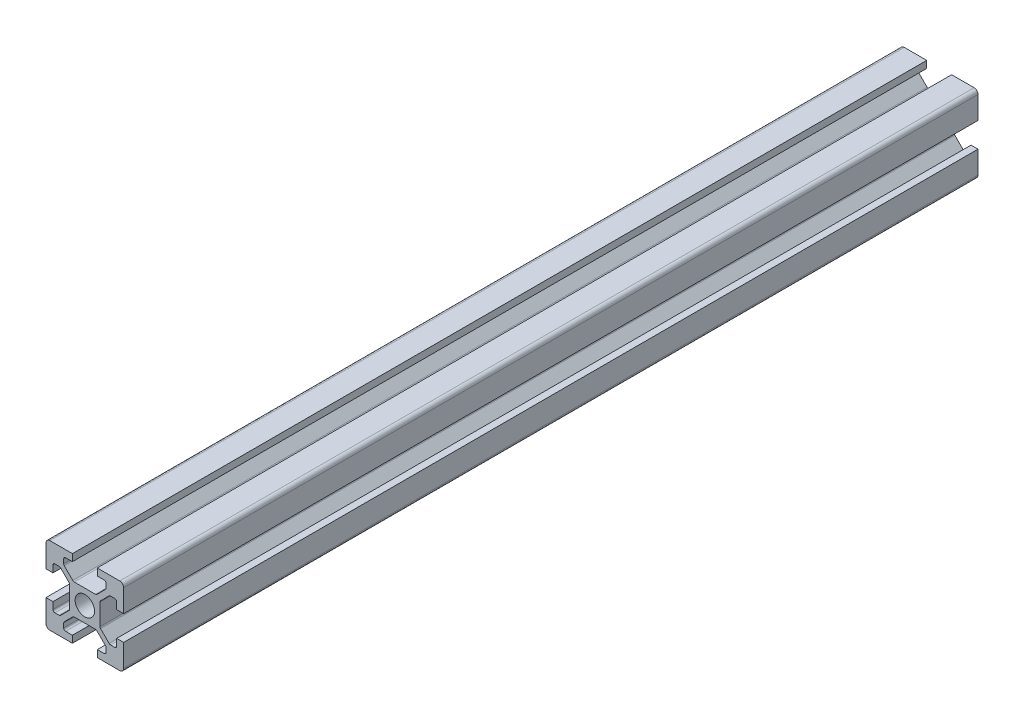
SolidWorks part; units mm, degrees
material "1060 Alloy"
ref_plane "Front Plane" through (0, 0, 0) normal (0, 0, 1) x (1, 0, 0)
ref_plane "Top Plane" through (0, 0, 0) normal (0, 1, 0) x (1, 0, 0)
ref_plane "Right Plane" through (0, 0, 0) normal (1, 0, 0) x (0, 0, -1)
sketch "Sketch1" plane through (0, 0, 0) normal (0, 0, 1) x (1, 0, 0)
  line L0 (20, 0) -> (-8.059, 28.059) construction
  line L1 (0, 0) -> (6.8, 0)
  line L2 (0, 0) -> (0, 6.8)
  line L3 (0, 20) -> (6.8, 20)
  line L4 (20, 0) -> (20, 6.8)
  line L5 (6.8, 20) -> (6.8, 18.2)
  line L6 (20, 20) -> (8.2322, 8.2322) construction
  line L7 (12.95, 6.1) -> (7.05, 6.1)
  line L8 (13.9, 7.05) -> (13.9, 12.95)
  line L9 (12.95, 13.9) -> (7.05, 13.9)
  line L10 (6.1, 7.05) -> (6.1, 12.95)
  line L11 (13.9, 6.1) -> (6.1, 13.9) construction
  line L12 (13.9, 13.9) -> (6.1, 6.1) construction
  line L13 (4.55, 16.4) -> (7.05, 13.9)
  line L14 (13.2, 18.2) -> (13.2, 20)
  line L15 (1.8, 6.8) -> (0, 6.8)
  line L16 (0, 13.2) -> (0, 20)
  line L17 (0, 13.2) -> (1.8, 13.2)
  line L18 (10, 10) -> (10, 13.9) construction
  line L19 (16.4, 4.55) -> (13.9, 7.05)
  line L20 (4.55, 16.4) -> (4.55, 18.2)
  line L21 (4.55, 18.2) -> (6.8, 18.2)
  line L22 (13.2, 18.2) -> (15.45, 18.2)
  line L23 (15.45, 18.2) -> (15.45, 16.4)
  line L24 (15.45, 16.4) -> (12.95, 13.9)
  line L25 (16.4, 4.55) -> (18.2, 4.55)
  line L26 (18.2, 4.55) -> (18.2, 6.8)
  line L27 (20, 6.8) -> (18.2, 6.8)
  line L28 (18.2, 13.2) -> (20, 13.2)
  line L29 (18.2, 13.2) -> (18.2, 15.45)
  line L30 (18.2, 15.45) -> (16.4, 15.45)
  line L31 (16.4, 15.45) -> (13.9, 12.95)
  line L32 (1.8, 4.55) -> (3.6, 4.55)
  line L33 (3.6, 15.45) -> (6.1, 12.95)
  line L34 (3.6, 15.45) -> (1.8, 15.45)
  line L35 (1.8, 15.45) -> (1.8, 13.2)
  line L36 (0, 13.2) -> (1.8, 13.2)
  line L37 (1.8, 6.8) -> (0, 6.8)
  line L38 (3.6, 4.55) -> (6.1, 7.05)
  line L39 (1.8, 6.8) -> (1.8, 4.55)
  line L40 (15.45, 3.6) -> (12.95, 6.1)
  line L41 (4.55, 3.6) -> (7.05, 6.1)
  line L42 (4.55, 1.8) -> (4.55, 3.6)
  line L43 (6.8, 1.8) -> (4.55, 1.8)
  line L44 (6.8, 1.8) -> (6.8, 0)
  line L45 (15.45, 3.6) -> (15.45, 1.8)
  line L46 (15.45, 1.8) -> (13.2, 1.8)
  line L47 (13.2, 0) -> (13.2, 1.8)
  line L48 (13.2, 20) -> (20, 20)
  line L49 (20, 13.2) -> (20, 20)
  line L50 (13.2, 0) -> (20, 0)
  line L51 (6.1, 6.1) -> (-5.5045, -5.5045) construction
  circle A0 centre (10, 10) radius 2.5
  point P25 (10, 16.4)
  point P39 (13.2, 19.1)
  point P46 (0.9, 6.8)
  dimension "D3" = 5
  dimension "D2" = 20
  dimension "D4" = 7.8
  dimension "D5" = 7.8
  dimension "D6" = 6.8
  dimension "D7" = 6.8
  dimension "D8" = 1.8
  dimension "D9" = 10.9
  dimension "D10" = 1.8
  dimension "D11" = 10.9
  dimension "D12" = 20
extrude "Boss-Extrude1" add sketch "Sketch1" along normal blind 220 contours L47 L50 L4 L27 L26 L25 L19 L8 L31 L30 L29 L28 L49 L48 L14 L22 L23 L24 L9 L13 L20 L21 L5 L3 L16 L17 L35 L34 L33 L10 L38 L32 L39 L15 L2 L1 L44 L43 L42 L41 L7 L40 L45 L46 A0 region at (0.2828, 3.4, 0)
fillet "Fillet1" radius 1 4 edges at (20, 20, 110) (20, 0, 110) (0, 0, 110) (0, 20, 110)
fillet "Fillet2" radius 0.5 6 edges at (4.55, 18.2, 110) (4.55, 16.4, 110) (7.05, 13.9, 110) (15.45, 18.2, 110) (15.45, 16.4, 110) (12.95, 13.9, 110)
fillet "Fillet3" radius 0.5 6 edges at (18.2, 15.45, 110) (16.4, 15.45, 110) (13.9, 12.95, 110) (18.2, 4.55, 110) (13.9, 7.05, 110) (16.4, 4.55, 110)
fillet "Fillet4" radius 0.5 6 edges at (1.8, 15.45, 110) (3.6, 15.45, 110) (6.1, 12.95, 110) (3.6, 4.55, 110) (1.8, 4.55, 110) (6.1, 7.05, 110)
fillet "Fillet5" radius 0.5 6 edges at (7.05, 6.1, 110) (4.55, 3.6, 110) (4.55, 1.8, 110) (15.45, 1.8, 110) (15.45, 3.6, 110) (12.95, 6.1, 110)
